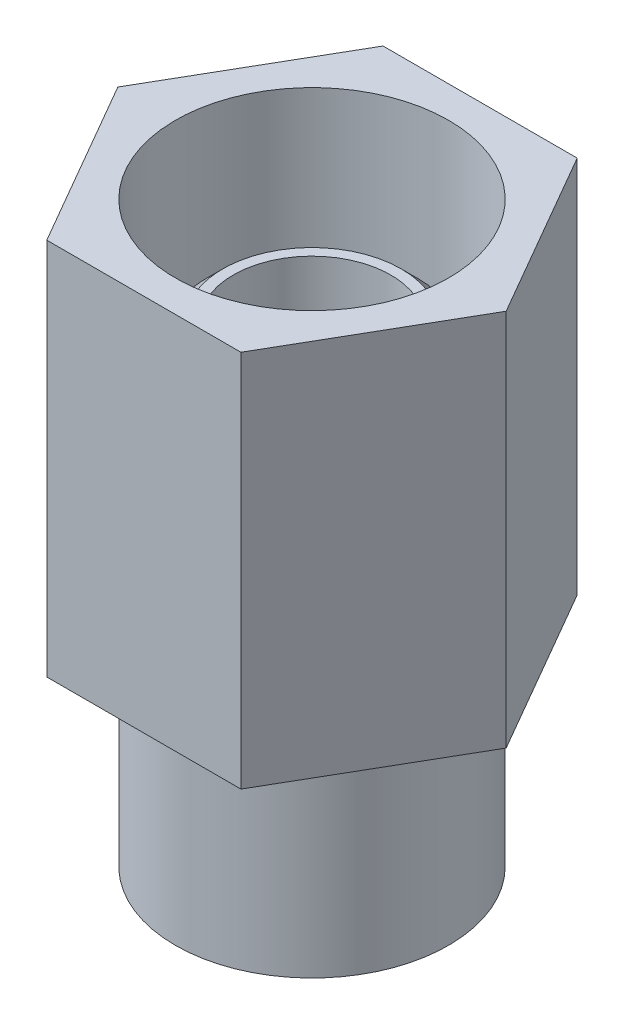
SolidWorks part; units mm, degrees
ref_plane "Front Plane" through (0, 0, 0) normal (0, 0, 1) x (1, 0, 0)
ref_plane "Top Plane" through (0, 0, 0) normal (0, 1, 0) x (1, 0, 0)
ref_plane "Right Plane" through (0, 0, 0) normal (1, 0, 0) x (0, 0, -1)
sketch "Szkic1" plane through (0, 0, 0) normal (0, 1, 0) x (1, 0, 0)
  line L1 (-18.4752, 0) -> (-9.2376, -16)
  line L2 (-9.2376, -16) -> (9.2376, -16)
  line L3 (9.2376, -16) -> (18.4752, 0)
  line L4 (18.4752, 0) -> (9.2376, 16)
  line L5 (9.2376, 16) -> (-9.2376, 16)
  line L6 (-9.2376, 16) -> (-18.4752, 0)
  circle A0 centre (0, 0) radius 13
  circle A1 centre (0, 0) radius 12
  circle A2 centre (0, 0) radius 7.5
  circle A3 centre (0, 0) radius 16
  circle A4 centre (0, 0) radius 16 construction
  dimension "D1" = 26
  dimension "D2" = 24
  dimension "D3" = 15
  dimension "D4" = 32
  dimension "D5" = 16
extrude "Dodanie-wyciągnięcie1" add sketch "Szkic1" along normal blind 19 contours A1 A2 | A0 A1 region at (-12.6323, 0, 0) region at (-11.6606, 0, 0)
chamfer "Sfazowanie1" distance 4.5 angle 45 1 edges at (0, 0, 7.5)
extrude "Dodanie-wyciągnięcie2" add sketch "Szkic1<3>" along normal blind 16 from offset 19 contours A3 A0 | A3 L5 L6 | A3 L6 L1 | A3 L1 L2 | A3 L2 L3 | A3 L3 L4 | A3 L4 L5 | A1 A2 | A0 A1 region at (-16.537, 0, 0) region at (-8.2685, 0, 14.3215) region at (-15.5475, 0, 0) region at (-8.2685, 0, -14.3215) region at (8.2685, 0, 14.3215) region at (8.2685, 0, -14.3215) region at (16.537, 0, 0) region at (-12.6323, 0, 0) region at (-11.6606, 0, 0)
sketch "Szkic1<3>" plane through (0, 0, 0) normal (0, 1, 0) x (1, 0, 0) same geometry as "Szkic1"
sketch "Szkic2" plane through (0, 0, 0) normal (0, 1, 0) x (1, 0, 0)
  line L1 (-9.2376, 16) -> (-18.4752, 0)
  line L2 (-18.4752, 0) -> (-9.2376, -16)
  line L3 (-9.2376, -16) -> (9.2376, -16)
  line L4 (9.2376, -16) -> (18.4752, 0)
  line L5 (18.4752, 0) -> (9.2376, 16)
  line L6 (9.2376, 16) -> (-9.2376, 16)
  circle A0 centre (0, 0) radius 13
  circle A1 centre (0, 0) radius 16
  circle A2 centre (0, 0) radius 16 construction
  circle A3 centre (0, 0) radius 7.5
  circle A4 centre (0, 0) radius 10
  dimension "D1" = 26
  dimension "D2" = 32
  dimension "D3" = 20
extrude "Dodanie-wyciągnięcie3" add sketch "Szkic2" along normal blind 26 from offset 29 contours A1 L6 L1 | A1 L1 L2 | A1 A0 | A1 L2 L3 | A1 L3 L4 | A1 L4 L5 | A1 L5 L6 region at (-8.2685, 0, -14.3215) region at (-16.537, 0, 0) region at (-7.7737, 0, -13.4645) region at (8.2685, 0, -14.3215) region at (-8.2685, 0, 14.3215) region at (16.537, 0, 0) region at (8.2685, 0, 14.3215)
extrude "Dodanie-wyciągnięcie4" add sketch "Szkic2<3>" along normal blind 16 from offset 29 contours A4 A3 region at (-9.7172, 0, 0)
sketch "Szkic2<3>" plane through (0, 0, 0) normal (0, 1, 0) x (1, 0, 0) same geometry as "Szkic2"
chamfer "Sfazowanie2" distance 1.5 angle 45 1 edges at (0, 45, 10)
